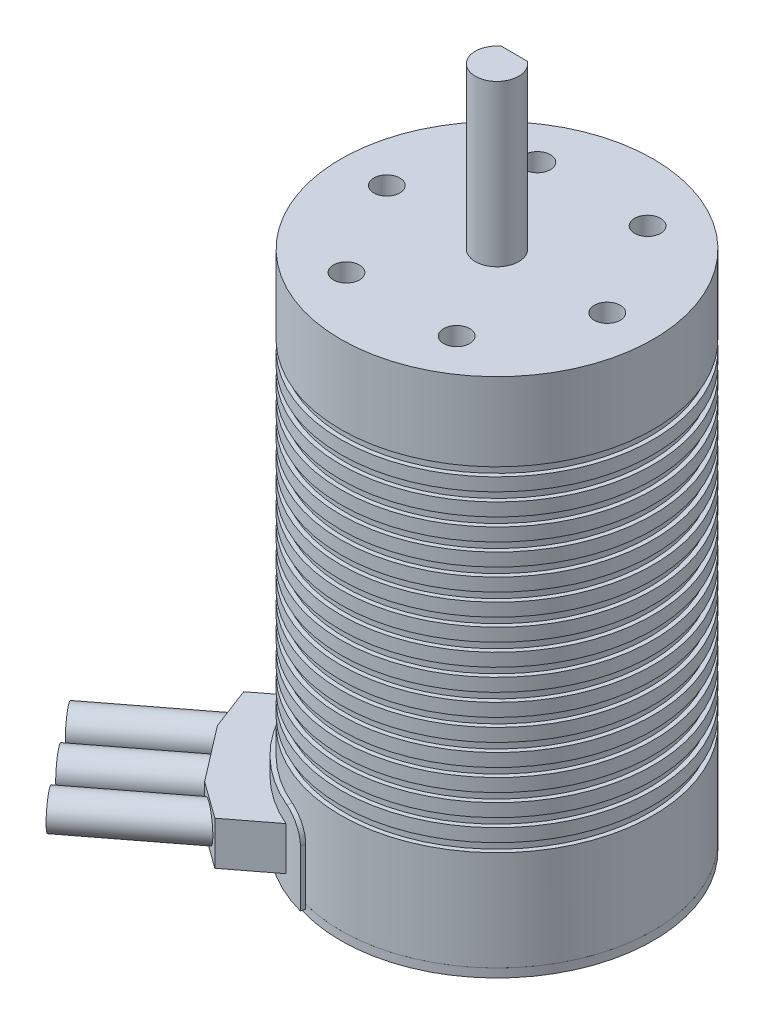
SolidWorks part; units mm, degrees
ref_plane "Ön Düzlem" through (0, 0, 0) normal (0, 0, 1) x (1, 0, 0)
ref_plane "Üst Düzlem" through (0, 0, 0) normal (0, 1, 0) x (1, 0, 0)
ref_plane "Sağ Düzlem" through (0, 0, 0) normal (1, 0, 0) x (0, 0, -1)
sketch "Sketch2" plane through (0, 0, 0) normal (0, 1, 0) x (1, 0, 0)
  circle A0 centre (0, 0) radius 18
  dimension "D1" = 36
extrude "Boss-Extrude1" add sketch "Sketch2" along normal blind 60
sketch "Sketch3" plane through (0, 60, 0) normal (0, 1, 0) x (1, 0, 0)
  circle A0 centre (0, 0) radius 2.5
  dimension "D1" = 5
extrude "Boss-Extrude2" add sketch "Sketch3" along normal blind 3 separate body
sketch "Sketch4" plane through (0, 63, 0) normal (0, 1, 0) x (1, 0, 0)
  line L0 (-1.5, 2) -> (1.5, 2)
  line L1 (0, 2) -> (0, -2.5) construction
  arc A0 (-1.5, 2) -> (1.5, 2) centre (0, 0) ccw
  dimension "D1" = 5
  dimension "D2" = 4.5
extrude "Boss-Extrude3" add sketch "Sketch4" along normal blind 15.5
sketch "Sketch8" plane through (0, 60, 0) normal (0, 1, 0) x (1, 0, 0)
  line L0 (12.7, 0) -> (-12.7, 0) construction
  circle A0 centre (-12.7, 0) radius 1.5
  circle A1 centre (-6.35, 10.9985) radius 1.5
  circle A2 centre (6.35, 10.9985) radius 1.5
  circle A3 centre (12.7, 0) radius 1.5
  circle A4 centre (6.35, -10.9985) radius 1.5
  circle A5 centre (-6.35, -10.9985) radius 1.5
  point P8 (0, 0)
  point P19 (0, 0)
  dimension "D1" = 3
  dimension "D2" = 25.4
  dimension "D3" = 6
extrude "Cut-Extrude1" cut sketch "Sketch8" against normal blind 5.5
sketch "Sketch9" plane through (0, 0, 0) normal (0, 0, 1) x (1, 0, 0)
  line L0 (18, 0) -> (18, 60) construction
  line L1 (18, 51) -> (17.5, 51)
  line L2 (18, 51) -> (18, 50)
  line L3 (18, 50) -> (17.5, 50)
  line L4 (17.5, 51) -> (17.5, 50)
  line L5 (18, 60) -> (-18, 60) construction
  line L6 (18, 50) -> (18, 48.5) construction
  line L7 (0, 0) -> (0, 60) construction
  line L8 (18, 48.5) -> (17.5, 48.5)
  line L9 (18, 48.5) -> (18, 47.5)
  line L10 (17.5, 48.5) -> (17.5, 47.5)
  line L11 (18, 47.5) -> (17.5, 47.5)
  line L12 (18, 47.5) -> (18, 46) construction
  line L13 (18, 46) -> (17.5, 46)
  line L14 (18, 46) -> (18, 45)
  line L15 (17.5, 46) -> (17.5, 45)
  line L16 (18, 45) -> (17.5, 45)
  line L17 (18, 45) -> (18, 43.5) construction
  line L18 (18, 43.5) -> (17.5, 43.5)
  line L19 (18, 43.5) -> (18, 42.5)
  line L20 (17.5, 43.5) -> (17.5, 42.5)
  line L21 (18, 42.5) -> (17.5, 42.5)
  line L22 (18, 42.5) -> (18, 41) construction
  line L23 (18, 41) -> (17.5, 41)
  line L24 (18, 41) -> (18, 40)
  line L25 (17.5, 41) -> (17.5, 40)
  line L26 (18, 40) -> (17.5, 40)
  line L27 (18, 40) -> (18, 38.5) construction
  line L28 (18, 38.5) -> (17.5, 38.5)
  line L29 (18, 38.5) -> (18, 37.5)
  line L30 (17.5, 38.5) -> (17.5, 37.5)
  line L31 (18, 37.5) -> (17.5, 37.5)
  line L32 (18, 37.5) -> (18, 36) construction
  line L33 (18, 36) -> (17.5, 36)
  line L34 (18, 36) -> (18, 35)
  line L35 (17.5, 36) -> (17.5, 35)
  line L36 (18, 35) -> (17.5, 35)
  line L37 (18, 35) -> (18, 33.5) construction
  line L38 (18, 33.5) -> (17.5, 33.5)
  line L39 (18, 33.5) -> (18, 32.5)
  line L40 (17.5, 33.5) -> (17.5, 32.5)
  line L41 (18, 32.5) -> (17.5, 32.5)
  line L42 (18, 32.5) -> (18, 31) construction
  line L43 (18, 31) -> (17.5, 31)
  line L44 (18, 31) -> (18, 30)
  line L45 (17.5, 31) -> (17.5, 30)
  line L46 (18, 30) -> (17.5, 30)
  line L47 (18, 30) -> (18, 28.5) construction
  line L48 (18, 28.5) -> (17.5, 28.5)
  line L49 (18, 28.5) -> (18, 27.5)
  line L50 (17.5, 28.5) -> (17.5, 27.5)
  line L51 (18, 27.5) -> (17.5, 27.5)
  line L52 (18, 27.5) -> (18, 26) construction
  line L53 (18, 26) -> (17.5, 26)
  line L54 (18, 26) -> (18, 25)
  line L55 (17.5, 26) -> (17.5, 25)
  line L56 (18, 25) -> (17.5, 25)
  line L57 (18, 25) -> (18, 23.5) construction
  line L58 (18, 23.5) -> (17.5, 23.5)
  line L59 (18, 23.5) -> (18, 22.5)
  line L60 (17.5, 23.5) -> (17.5, 22.5)
  line L61 (18, 22.5) -> (17.5, 22.5)
  line L62 (18, 22.5) -> (18, 21) construction
  line L63 (18, 21) -> (17.5, 21)
  line L64 (18, 21) -> (18, 20)
  line L65 (17.5, 21) -> (17.5, 20)
  line L66 (18, 20) -> (17.5, 20)
  line L67 (18, 20) -> (18, 18.5) construction
  line L68 (18, 18.5) -> (17.5, 18.5)
  line L69 (18, 18.5) -> (18, 17.5)
  line L70 (17.5, 18.5) -> (17.5, 17.5)
  line L71 (18, 17.5) -> (17.5, 17.5)
  line L72 (18, 17.5) -> (18, 16) construction
  line L73 (18, 16) -> (17.5, 16)
  line L74 (18, 16) -> (18, 15)
  line L75 (17.5, 16) -> (17.5, 15)
  line L76 (18, 15) -> (17.5, 15)
  line L77 (18, 15) -> (18, 13.5) construction
  line L78 (18, 13.5) -> (17.5, 13.5)
  line L79 (18, 13.5) -> (18, 12.5)
  line L80 (17.5, 13.5) -> (17.5, 12.5)
  line L81 (18, 12.5) -> (17.5, 12.5)
  line L82 (18, 12.5) -> (18, 11) construction
  line L83 (-18, 0) -> (18, 0) construction
  dimension "D1" = 0.5
  dimension "D2" = 9
  dimension "D3" = 1
  dimension "D4" = 1.5
  dimension "D5" = 16
  dimension "D6" = 12.5
revolve "Cut-Revolve1" cut sketch "Sketch9" angle 360 about L7 region at (17.75, 50.5, 0) region at (17.75, 48, 0) region at (17.75, 45.5, 0) region at (17.75, 43, 0) region at (17.75, 40.5, 0) region at (17.75, 35.5, 0) region at (17.75, 28, 0) region at (17.75, 18, 0)
sketch "Sketch10" plane through (0, 0, 0) normal (0, -1, 0) x (1, 0, 0)
  circle A1 centre (0, 0) radius 18
  circle A2 centre (0, 0) radius 18
  dimension "D1" = 0
extrude "Cut-Extrude2" cut sketch "Sketch10" against normal blind 1
sketch "Sketch11" plane through (0, 1, 0) normal (0, -1, 0) x (1, 0, 0)
  circle A1 centre (0, 0) radius 18
  circle A2 centre (0, 0) radius 18
  dimension "D1" = 0
extrude "Boss-Extrude4" add sketch "Sketch11" along normal blind 1 separate body
sketch "Sketch12" plane through (0, 0, 0) normal (0, 0, 1) x (1, 0, 0)
  line L0 (-18, 12.5) -> (-18, 1) construction
  line L1 (-18, 9.5) -> (-18.5, 9.5)
  line L2 (-18, 9.5) -> (-18, 0.5)
  line L3 (-18, 0.5) -> (-18.5, 0.5)
  line L4 (-18.5, 9.5) -> (-18.5, 0.5)
  line L5 (-18, 0) -> (18, 0) construction
  line L6 (0, 0) -> (0, 60) construction
  line L7 (18, 60) -> (-18, 60) construction
  dimension "D1" = 9
  dimension "D2" = 0.5
  dimension "D3" = 0.5
revolve "Revolve1" add sketch "Sketch12" angle 75 about L6
fillet "Fillet1" radius 2.5 2 edges at (-4.7234, 9.5, 17.6281) (-18.25, 9.5, 0)
ref_plane "Plane2" through (0, 0, 0) normal (0.6088, 0, 0.7934) x (0.7934, 0, -0.6088)
sketch "Sketch14" plane through (0, 0, 0) normal (0.6088, 0, 0.7934) x (0.7934, 0, -0.6088)
  line L11 (-16.0643, 9.5) -> (-18.5, 9.5) construction
  line L12 (-18.5, 7.5) -> (-23.5, 7.5)
  line L13 (-18.5, 7.5) -> (-18.5, 2.5)
  line L14 (-18.5, 2.5) -> (-23.5, 2.5)
  line L15 (-23.5, 7.5) -> (-23.5, 2.5)
  line L16 (-18.5, 0.5) -> (-14.677, 0.5) construction
  line L17 (-14.2804, 1) -> (-14.2804, 7) construction
  line L18 (-18.5, 7.5) -> (-14.2804, 7.5)
  line L19 (-18.5, 7.5) -> (-18.5, 2.5)
  line L20 (-18.5, 2.5) -> (-14.2804, 2.5)
  line L21 (-14.2804, 7.5) -> (-14.2804, 2.5)
  dimension "D1" = 18.5
  dimension "D2" = 2
  dimension "D3" = 2
  dimension "D4" = 5
extrude "Boss-Extrude5" add sketch "Sketch14" along normal mid plane 18 contours L12 L15 L14 L13 | L13 region at (-16.6604, 5, 12.784) region at (-13.0032, 5, 9.9777)
chamfer "Chamfer1" distance 1.5 distance2 5 1 edges at (-24.1227, 5, 7.1657) first distance on face at (-21.2123, 5, 4.9325)
chamfer "Chamfer2" distance 5 distance2 1.5 1 edges at (-13.165, 5, 21.4461) first distance on face at (-17.1219, 5, 16.2893)
sketch "Sketch15" plane through (-18.6438, 0, 14.3059) normal (-0.7934, 0, 0.6088) x (0.6088, 0, 0.7934)
  line L0 (0, 2.5) -> (0, 7.5) construction
  line L1 (4, 7.5) -> (-4, 7.5) construction
  line L2 (-9, 2.5) -> (9, 2.5) construction
  line L3 (6, 5) -> (-6, 5) construction
  circle A0 centre (0, 5) radius 2
  circle A1 centre (6, 5) radius 2
  circle A2 centre (-6, 5) radius 2
  point P7 (0, 5)
  point P15 (0, 5)
  dimension "D1" = 4
  dimension "D2" = 2
  dimension "D4" = 12
  dimension "D3" = 2
extrude "Boss-Extrude6" add sketch "Sketch15" along normal mid plane 25
